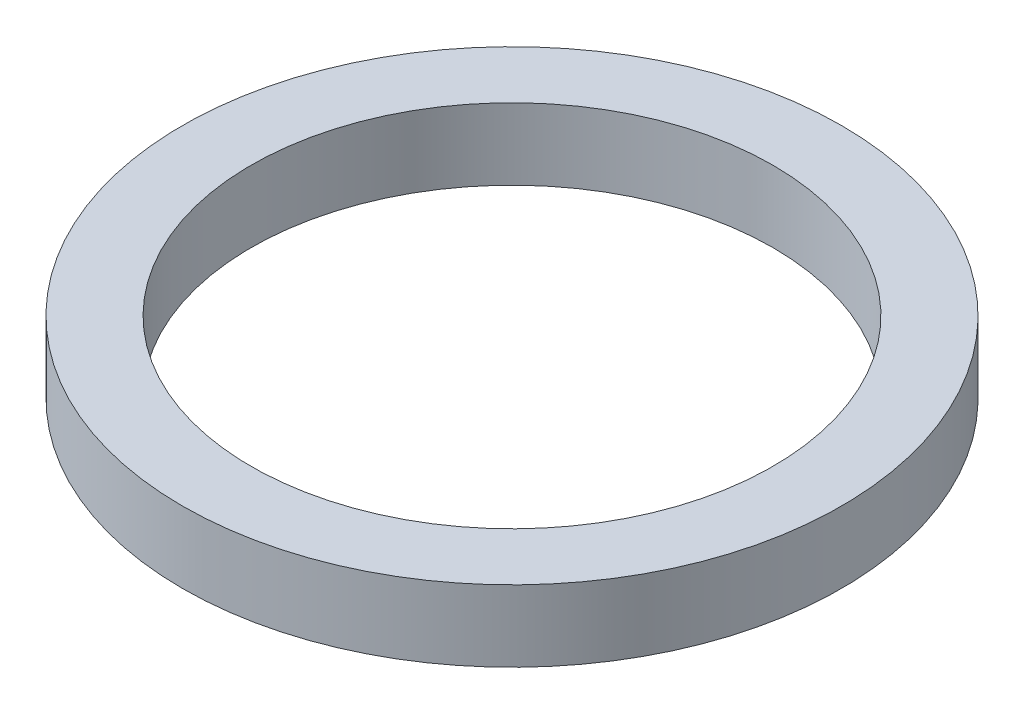
SolidWorks part; units mm, degrees
ref_plane "Front Plane" through (0, 0, 0) normal (0, 0, 1) x (1, 0, 0)
ref_plane "Top Plane" through (0, 0, 0) normal (0, 1, 0) x (1, 0, 0)
ref_plane "Right Plane" through (0, 0, 0) normal (1, 0, 0) x (0, 0, -1)
sketch "Sketch1" plane through (0, 0, 0) normal (0, 1, 0) x (1, 0, 0)
  circle A0 centre (0, 0) radius 60
  dimension "FLANGE_OD" = 120
extrude "Boss-Extrude1" add sketch "Sketch1" along normal blind 13
sketch "Sketch2" plane through (0, 0, 0) normal (0, 1, 0) x (1, 0, 0)
  circle A0 centre (0, 0) radius 47.5
  dimension "BORE_D" = 95
extrude "Cut-Extrude1" cut sketch "Sketch2" along normal through all
sketch "Sketch3" plane through (0, 13, 0) normal (0, 1, 0) x (1, 0, 0)
  circle A0 centre (0, 0) radius 25.5026 construction
  circle A1 centre (-25.5026, 0) radius 2.1742
  dimension "BOLT_D" = 4.3484
  dimension "BOLT_PCD" = 51.0053
extrude "Cut-Extrude2" cut sketch "Sketch3" against normal blind 9.6601 rebuild error yes
pattern_circular "CirPattern1" count 8 over 360 rebuild error yes
